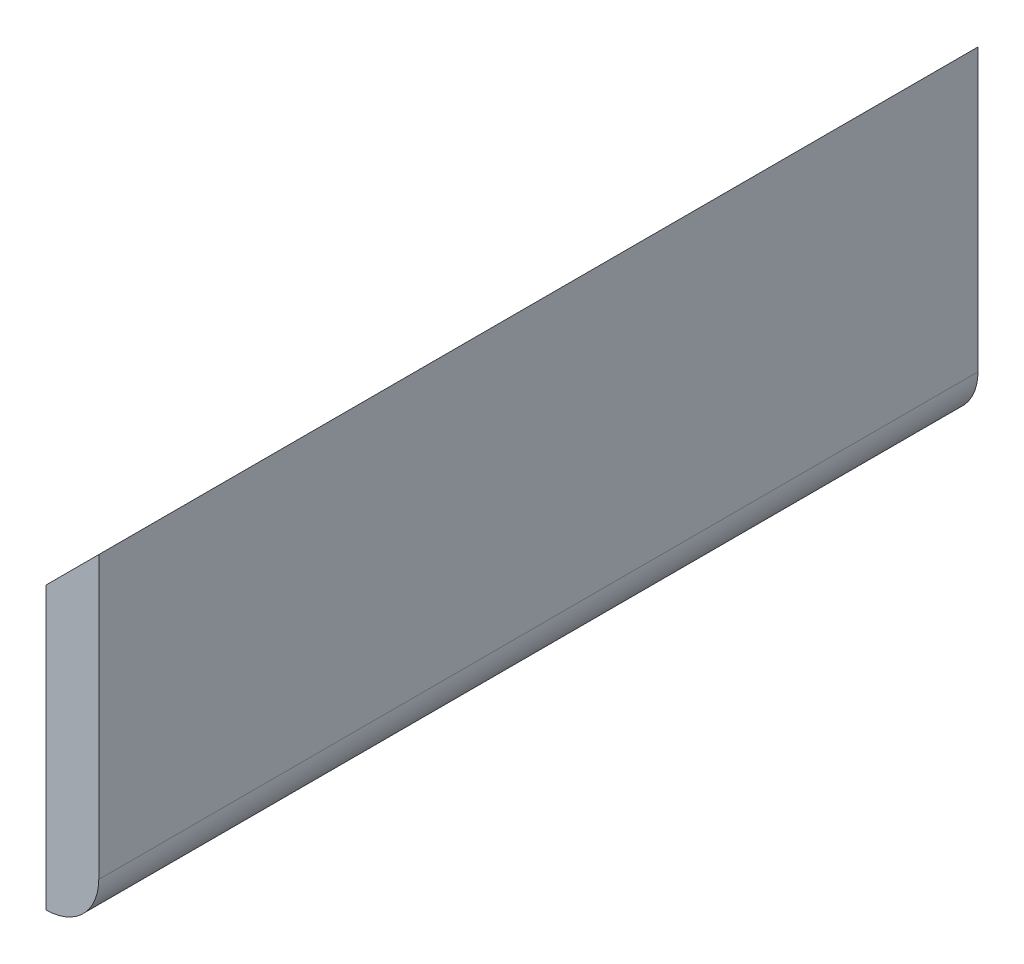
SolidWorks part; units mm, degrees
ref_plane "Front Plane" through (0, 0, 0) normal (1, 0, 0) x (0, 1, 0)
ref_plane "Top Plane" through (0, 0, 0) normal (0, 0, 1) x (0, 1, 0)
ref_plane "Right Plane" through (0, 0, 0) normal (0, 1, 0) x (-1, 0, 0)
sketch "Sketch2" plane through (0, 0, 0) normal (0, 0, 1) x (0, 1, 0)
  line L6 (3.873, 1) -> (16, 1)
  line L8 (3.873, -1) -> (16, -1)
  line L9 (16, 1) -> (16, -1)
  circle A3 centre (0, 0) radius 2.25
  arc A4 (3.873, 1) -> (3.873, -1) centre (0, 0) ccw
  dimension "D1" = 4.5
  dimension "D2" = 8
  dimension "D3" = 12.127
  dimension "D4" = 2
  dimension "D6" = 16
extrude "Boss-Extrude2" add sketch "Sketch2" along normal blind 5
sketch "Sketch4" plane through (0, 0, 0) normal (0, 0, -1) x (1, 0, 0)
  line L1 (-2.5, 5.5) -> (2.5, 5.5)
  line L2 (-7.5, 0.5) -> (-7.5, -19.5)
  line L3 (-7.5, -19.5) -> (7.5, -19.5)
  line L4 (7.5, 0.5) -> (7.5, -19.5)
  arc A0 (2.5, 5.5) -> (7.5, 0.5) centre (2.5, 0.5) cw
  arc A1 (-2.5, 5.5) -> (-7.5, 0.5) centre (-2.5, 0.5) ccw
  point P4 (0, 5.5)
  point P8 (7.5, 5.5)
  point P11 (-7.5, 5.5)
  dimension "D4" = 5
  dimension "D1" = 5.5
  dimension "D2" = 25
  dimension "D3" = 15
extrude "Boss-Extrude3" add sketch "Sketch4" against normal blind 85 contours L4 L3 L2 A1 L1 A0
extrude "Cut-Extrude1" cut sketch "Sketch2<2>" along normal blind 5
sketch "Sketch2<2>" plane through (0, 0, 0) normal (0, 0, 1) x (0, 1, 0) same geometry as "Sketch2"
sketch "Sketch5" plane through (7.5, 0, 0) normal (1, 0, 0) x (0, 1, 0)
  line L0 (19.5, 42.5) -> (-0.5, 42.5) construction
  line L1 (19.5, 85) -> (19.5, 0) construction
  line L2 (-0.5, 85) -> (-0.5, 0) construction
  line L3 (19.5, 42.5) -> (-0.5, 42.5) construction
sketch "Sketch6" plane through (-7.5, 0, 0) normal (-1, 0, 0) x (0, -1, 0)
  line L0 (-19.5, 42.5) -> (0.5, 42.5) construction
  line L1 (0.5, 85) -> (0.5, 0) construction
ref_plane "Plane1" through (0, 0, 42.5) normal (0, 0, 1) x (1, 0, 0)
mirror "Mirror1" about plane through (0, 0, 42.5) normal (0, 0, 1) of "Cut-Extrude1"
sketch "Sketch9" plane through (7.5, 0, 0) normal (1, 0, 0) x (0, 1, 0)
  line L4 (-0.5, 0) -> (19.5, 0)
  line L5 (19.5, 0) -> (19.5, 85)
  line L6 (19.5, 85) -> (-0.5, 85)
  line L7 (-0.5, 85) -> (-0.5, 0)
  line L8 (-0.5, 0) -> (19.5, 0)
  line L9 (19.5, 0) -> (19.5, 85)
  line L10 (19.5, 85) -> (-0.5, 85)
  line L11 (-0.5, 85) -> (-0.5, 0)
  dimension "D1" = 0
extrude "Boss-Extrude6" add sketch "Sketch9" along normal blind 21.72
sketch "Sketch11" plane through (0, 19.5, 0) normal (0, 1, 0) x (-1, 0, 0)
  line L0 (7.5, 85) -> (-29.22, 85) construction
  line L1 (7.5, 0) -> (-29.22, 0) construction
  line L2 (-29.22, 0) -> (-29.22, 85) construction
  line L3 (-27.22, 0) -> (-14.22, 0)
  line L5 (-29.22, 167.5) -> (-29.22, -82.5)
  line L10 (-27.22, 0) -> (-27.22, 85)
  line L11 (-29.22, -82.5) -> (-14.22, -82.5)
  line L12 (-14.22, 0) -> (-14.22, -82.5)
  line L13 (-27.22, 85) -> (-14.22, 85)
  line L15 (-29.22, 167.5) -> (-14.22, 167.5)
  line L16 (-14.22, 85) -> (-14.22, 167.5)
  point P0 (-29.22, 42.5)
  dimension "D1" = 15
  dimension "D2" = 15
  dimension "D3" = 2
  dimension "D4" = 250
  dimension "D5" = 36.72
  dimension "D6" = 82.5
extrude "Boss-Extrude7" add sketch "Sketch11" along normal blind 75 and the other way blind 20
fillet "Fillet2" radius 15 1 edges at (29.22, -0.5, 42.5)
sketch "Sketch12" plane through (0, 94.5, 0) normal (0, 1, 0) x (-1, 0, 0)
  line L0 (-14.22, 167.5) -> (-29.22, 167.5) construction
  line L1 (-27.22, -80.5) -> (12.78, -80.5)
  line L2 (-27.22, -80.5) -> (-27.22, 165.5)
  line L3 (-27.22, 165.5) -> (12.78, 165.5)
  line L4 (12.78, -80.5) -> (12.78, 165.5)
  line L5 (-29.22, -82.5) -> (-14.22, -82.5) construction
  line L6 (-29.22, 167.5) -> (-29.22, -82.5) construction
  dimension "D1" = 2
  dimension "D2" = 2
  dimension "D3" = 2
  dimension "D4" = 40
extrude "Cut-Extrude2" cut sketch "Sketch12" against normal up to surface (75 mm away) up to face at (11.3133, 19.5, 42.5)
chamfer "Chamfer2" distance 15 angle 45 1 edges at (14.22, 94.5, 166.5)
